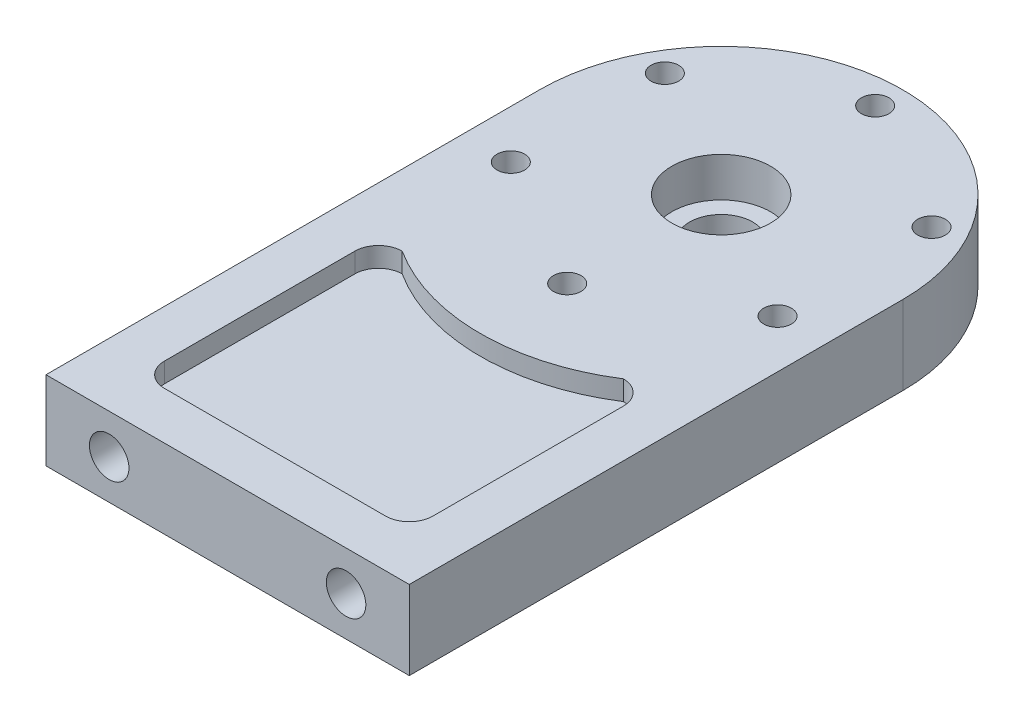
SolidWorks part; units mm, degrees
ref_plane "Front Plane" through (0, 0, 0) normal (0, 0, 1) x (1, 0, 0)
ref_plane "Top Plane" through (0, 0, 0) normal (0, 1, 0) x (1, 0, 0)
ref_plane "Right Plane" through (0, 0, 0) normal (1, 0, 0) x (0, 0, -1)
sketch "Sketch3" plane through (0, 0, 0) normal (0, 1, 0) x (1, 0, 0)
  line L1 (0, 0) -> (184, 0)
  line L2 (0, 0) -> (0, 250)
  line L3 (0, 250) -> (184, 250) construction
  line L4 (184, 0) -> (184, 250)
  arc A0 (184, 250) -> (0, 250) centre (92, 250) ccw
  circle A1 centre (92, 250) radius 78 construction
  dimension "D3" = 156
  dimension "D1" = 250
  dimension "D2" = 184
extrude "Boss-Extrude1" add sketch "Sketch3" along normal blind 40
sketch "Sketch5" plane through (0, 40, 0) normal (0, 1, 0) x (1, 0, 0)
  circle A0 centre (92, 250) radius 25
  dimension "D1" = 50
extrude "Cut-Extrude1" cut sketch "Sketch5" against normal blind 20
sketch "Sketch6" plane through (0, 0, 0) normal (0, -1, 0) x (1, 0, 0)
  circle A0 centre (92, -250) radius 16
  dimension "D1" = 32
extrude "Cut-Extrude2" cut sketch "Sketch6" against normal blind 20
sketch "Sketch7" plane through (0, 40, 0) normal (0, 1, 0) x (1, 0, 0)
  circle A0 centre (92, 250) radius 78 construction
  circle A1 centre (92, 328) radius 7
  dimension "D1" = 156
  dimension "D2" = 14
extrude "Cut-Extrude3" cut sketch "Sketch7" against normal blind 25
pattern_circular "CirPattern1" count 6 over 360 about axis through (92, 40, -250) along (0, 1, 0) of "Cut-Extrude3"
sketch "Sketch8" plane through (0, 0, 0) normal (0, -1, 0) x (1, 0, 0)
  circle A0 centre (92, -250) radius 78 construction
  circle A1 centre (92, -328) radius 12
  dimension "D1" = 156
  dimension "D2" = 24
extrude "Cut-Extrude4" cut sketch "Sketch8" against normal blind 15
pattern_circular "CirPattern2" count 6 over 360 about axis through (92, 0, -250) along (0, 1, 0) of "Cut-Extrude4"
sketch "Sketch9" plane through (0, 40, 0) normal (0, 1, 0) x (1, 0, 0)
  line L0 (0, 250) -> (0, 0) construction
  line L1 (36, 24) -> (148, 24)
  line L2 (24, 36) -> (24, 132.4208)
  line L3 (36, 144.4208) -> (148, 144.4208) construction
  line L4 (160, 36) -> (160, 132.4208)
  line L5 (184, 0) -> (184, 250) construction
  line L6 (0, 0) -> (184, 0) construction
  arc A0 (24, 36) -> (36, 24) centre (36, 36) ccw
  arc A1 (148, 24) -> (160, 36) centre (148, 36) ccw
  arc A2 (160, 132.4208) -> (148, 144.4208) centre (148, 132.4208) ccw
  arc A3 (24, 132.4208) -> (36, 144.4208) centre (36, 132.4208) cw
  arc A4 (148, 144.4208) -> (36, 144.4208) centre (92, 232.0564) cw
  dimension "D5" = 12
  dimension "D6" = 104
  dimension "D1" = 24
  dimension "D2" = 24
  dimension "D3" = 24
  dimension "D4" = 144.4208
extrude "Cut-Extrude5" cut sketch "Sketch9" against normal blind 10
ref_plane "Plane1" through (0, 20, 0) normal (0, 1, 0) x (1, 0, 0)
mirror "Mirror1" about plane through (0, 20, 0) normal (0, 1, 0) of "Cut-Extrude5"
ref_plane "Plane2" through (92, 0, 0) normal (1, 0, 0) x (0, 0, -1)
sketch "Sketch13" plane through (0, 0, 0) normal (0, 0, 1) x (1, 0, 0)
  line L0 (92, 0) -> (92, 40) construction
  line L1 (0, 0) -> (184, 0) construction
  line L2 (0, 40) -> (184, 40) construction
  circle A0 centre (32, 20) radius 10
  circle A1 centre (152, 20) radius 10
  dimension "D1" = 20
  dimension "D2" = 60
  dimension "D3" = 20
extrude "Cut-Extrude10" cut sketch "Sketch13" against normal blind 20
